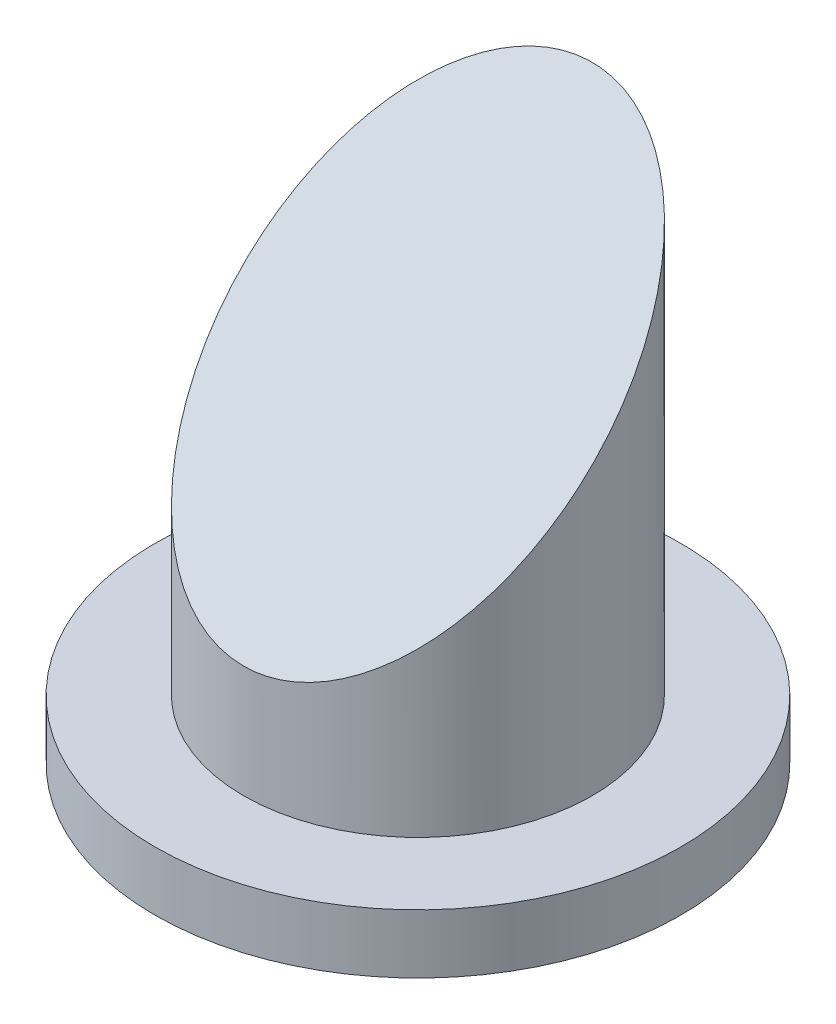
SolidWorks part; units mm, degrees
material "PTFE (general)"
ref_plane "Front Plane" through (0, 0, 0) normal (0, 0, 1) x (1, 0, 0)
ref_plane "Top Plane" through (0, 0, 0) normal (0, 1, 0) x (1, 0, 0)
ref_plane "Right Plane" through (0, 0, 0) normal (1, 0, 0) x (0, 0, -1)
sketch "Sketch1" plane through (0, 0, 0) normal (0, 1, 0) x (1, 0, 0)
  circle A0 centre (0, 0) radius 8.9
  dimension "D1" = 17.8
extrude "Boss-Extrude1" add sketch "Sketch1" along normal blind 2
sketch "Sketch2" plane through (0, 2, 0) normal (0, 1, 0) x (1, 0, 0)
  circle A0 centre (0, 0) radius 5.9
  dimension "D1" = 11.8
extrude "Boss-Extrude2" add sketch "Sketch2" along normal blind 20
sketch "Sketch3" plane through (0, 0, 0) normal (1, 0, 0) x (0, 0, -1)
  line L0 (-6.28, 5.42) -> (6.28, 17.98)
  line L2 (8.9, 2) -> (-8.9, 2) construction
  line L4 (-6.28, 5.42) -> (-6.28, 28.7719)
  line L5 (-6.28, 28.7719) -> (6.28, 28.7719)
  line L6 (6.28, 17.98) -> (6.28, 28.7719)
  point P2 (0, 11.7)
  dimension "D1" = 12.56
  dimension "D2" = 45
  dimension "D3" = 12.56
  dimension "D4" = 6.28
  dimension "D5" = 9.7
extrude "Cut-Extrude1" cut sketch "Sketch3" against normal through all both and the other way through all contours L0 L6 L5 L4 region at (0, 19.8509, 0.77)
sketch "Sketch4" plane through (0, 0, 0) normal (0, -1, 0) x (1, 0, 0)
  line L1 (-0.5, -3) -> (0.5, -3)
  line L2 (-0.5, -3) -> (-0.5, -5)
  line L3 (-0.5, -5) -> (0.5, -5)
  line L4 (0.5, -3) -> (0.5, -5)
  dimension "D1" = 2
  dimension "D2" = 1
  dimension "D3" = 0.5
  dimension "D4" = 5
extrude "Cut-Extrude2" cut sketch "Sketch4" against normal blind 1.2
fillet "Fillet1" radius 0.25 8 edges at (0, 1.2, -3) (0.5, 1.2, -4) (0, 1.2, -5) (-0.5, 1.2, -4) (-0.5, 0.6, -5) (-0.5, 0.6, -3) (0.5, 0.6, -5) (0.5, 0.6, -3)
